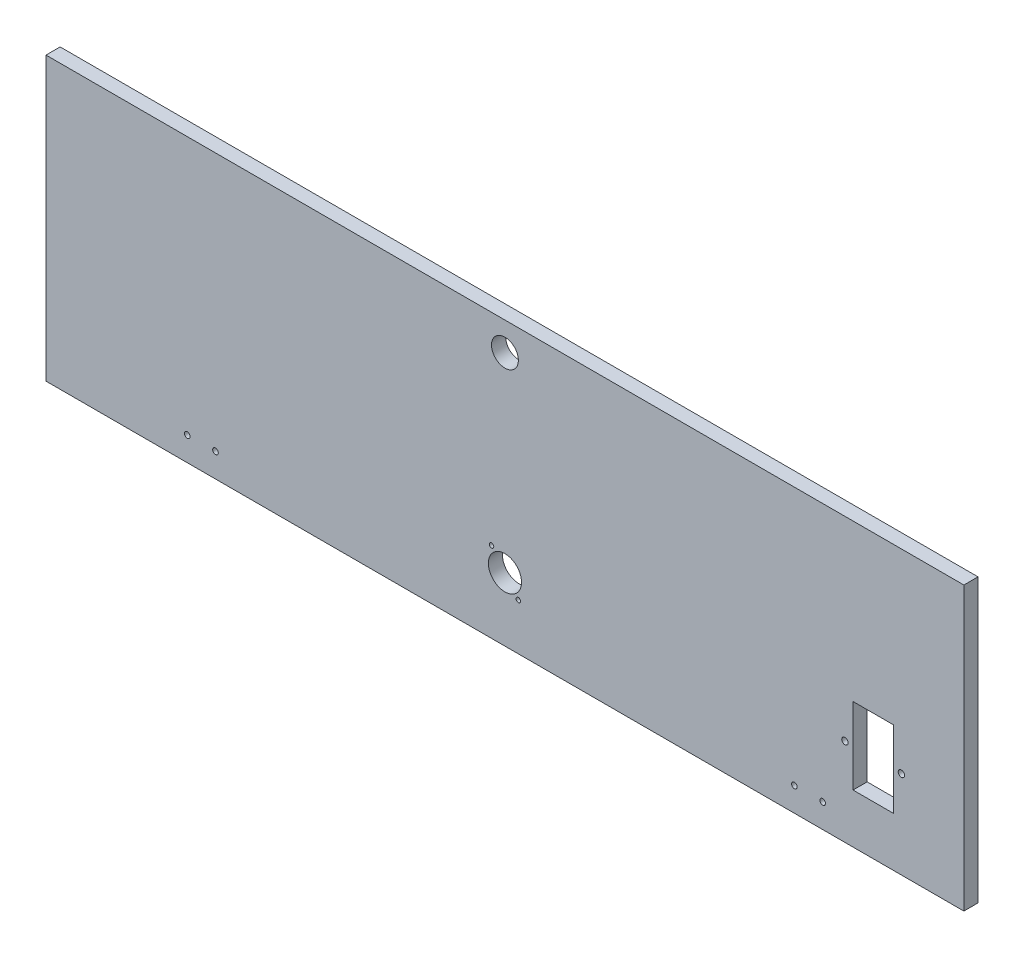
SolidWorks part; units mm, degrees
ref_plane "Plan de face" through (0, 0, 0) normal (0, 0, 1) x (1, 0, 0)
ref_plane "Plan de dessus" through (0, 0, 0) normal (0, 1, 0) x (1, 0, 0)
ref_plane "Plan de droite" through (0, 0, 0) normal (1, 0, 0) x (0, 0, -1)
sketch "Esquisse1" plane through (0, 0, 0) normal (0, 0, 1) x (1, 0, 0)
  line L1 (0, 0) -> (650, 0)
  line L2 (0, 0) -> (0, 200)
  line L3 (0, 200) -> (650, 200)
  line L4 (650, 0) -> (650, 200)
  dimension "D1" = 200
  dimension "D2" = 650
extrude "Boss.-Extru.1" add sketch "Esquisse1" along normal blind 10
sketch "Esquisse2" plane through (0, 0, 10) normal (0, 0, 1) x (1, 0, 0)
  line L4 (0, 200) -> (0, 0) construction
  line L5 (650, 0) -> (650, 200) construction
  line L6 (0, 0) -> (650, 0) construction
  circle A0 centre (100, 17) radius 2
  circle A1 centre (120, 17) radius 2
  circle A2 centre (530, 17) radius 2
  circle A3 centre (550, 17) radius 2
  dimension "D1" = 4
  dimension "D2" = 4
  dimension "D3" = 4
  dimension "D4" = 4
  dimension "D5" = 20
  dimension "D6" = 20
  dimension "D7" = 100
  dimension "D8" = 100
  dimension "D9" = 17
  dimension "D10" = 17
  dimension "D11" = 17
  dimension "D12" = 17
extrude "Enlèv. mat.-Extru.1" cut sketch "Esquisse2" against normal blind 10
sketch "Esquisse3" plane through (0, 0, 10) normal (0, 0, 1) x (1, 0, 0)
  line L0 (0, 0) -> (650, 0) construction
  line L1 (334.5004, 33.0006) -> (325, 45)
  line L2 (325, 45) -> (315.4996, 56.9994)
  line L3 (325, 45) -> (265.8175, 45)
  line L4 (325, 45) -> (364.3682, 45)
  line L5 (650, 0) -> (650, 200) construction
  line L6 (571.5, 35) -> (600, 35)
  line L7 (571.5, 35) -> (571.5, 89.3)
  line L8 (571.5, 89.3) -> (600, 89.3)
  line L9 (600, 35) -> (600, 89.3)
  circle A0 centre (325, 45) radius 11.75
  circle A1 centre (315.4996, 56.9994) radius 1.6
  circle A2 centre (334.5004, 33.0006) radius 1.6
  circle A3 centre (565.75, 62.15) radius 2.25
  circle A4 centre (605.75, 62.15) radius 2.25
  point P4 (325, 0)
  point P19 (585.75, 89.3)
  point P20 (571.5, 62.15)
  dimension "D1" = 23.5
  dimension "D4" = 3.2
  dimension "D5" = 3.2
  dimension "D14" = 4.5
  dimension "D15" = 4.5
  dimension "D2" = 0
  dimension "D3" = 45
  dimension "D6" = 30.61
  dimension "D7" = 15.305
  dimension "D8" = 51.63
  dimension "D9" = 180
  dimension "D10" = 51.63
  dimension "D11" = 15.305
  dimension "D12" = 28.5
  dimension "D13" = 54.3
  dimension "D16" = 40
  dimension "D17" = 20
  dimension "D18" = 0
  dimension "D19" = 35
  dimension "D20" = 50
  dimension "D21" = 20
extrude "Enlèv. mat.-Extru.2" cut sketch "Esquisse3" against normal blind 10 contours L3 A0 L1 | L4 A0 L2 | L1 A0 L4 | L2 A0 L3 | A1 | A2 | L6 L9 L8 L7 | A3 | A4 region at (314.1, 57.6764, 10) region at (322.2589, 39.3335, 10) region at (331.8154, 41.7031, 10) region at (335.1774, 34.4002, 10) region at (318.1846, 48.2969, 10) region at (327.7411, 50.6665, 10) region at (585.75, 62.15, 10)
sketch "Esquisse4" plane through (0, 0, 10) normal (0, 0, 1) x (1, 0, 0)
  line L0 (650, 200) -> (0, 200) construction
  circle A0 centre (325, 180) radius 9.5
  point P4 (325, 200)
  dimension "D1" = 19
  dimension "D3" = 20
  dimension "D2" = 0
extrude "Enlèv. mat.-Extru.3" cut sketch "Esquisse4" against normal blind 10
sketch "Esquisse5" plane through (0, 0, 0) normal (0, 0, 1) x (1, 0, 0)
  line L0 (650, 200) -> (0, 200) construction
  line L1 (650, 200) -> (0, 200) construction
  line L2 (0, 200) -> (0, 0) construction
  line L3 (650, 0) -> (650, 200) construction
  circle A0 centre (341, 180) radius 1
  circle A1 centre (309, 180) radius 1
  circle A2 centre (40, 190) radius 1
  circle A3 centre (20, 190) radius 1
  circle A4 centre (630, 190) radius 1
  circle A5 centre (610, 190) radius 1
  point P6 (325, 200)
  dimension "D2" = 2
  dimension "D3" = 2
  dimension "D7" = 2
  dimension "D8" = 2
  dimension "D9" = 2
  dimension "D10" = 2
  dimension "D1" = 32
  dimension "D4" = 16
  dimension "D5" = 20
  dimension "D6" = 20
  dimension "D11" = 20
  dimension "D12" = 10
  dimension "D13" = 10
  dimension "D14" = 20
  dimension "D15" = 10
  dimension "D16" = 10
  dimension "D17" = 20
  dimension "D18" = 20
extrude "Enlèv. mat.-Extru.4" cut sketch "Esquisse5" along normal blind 2
